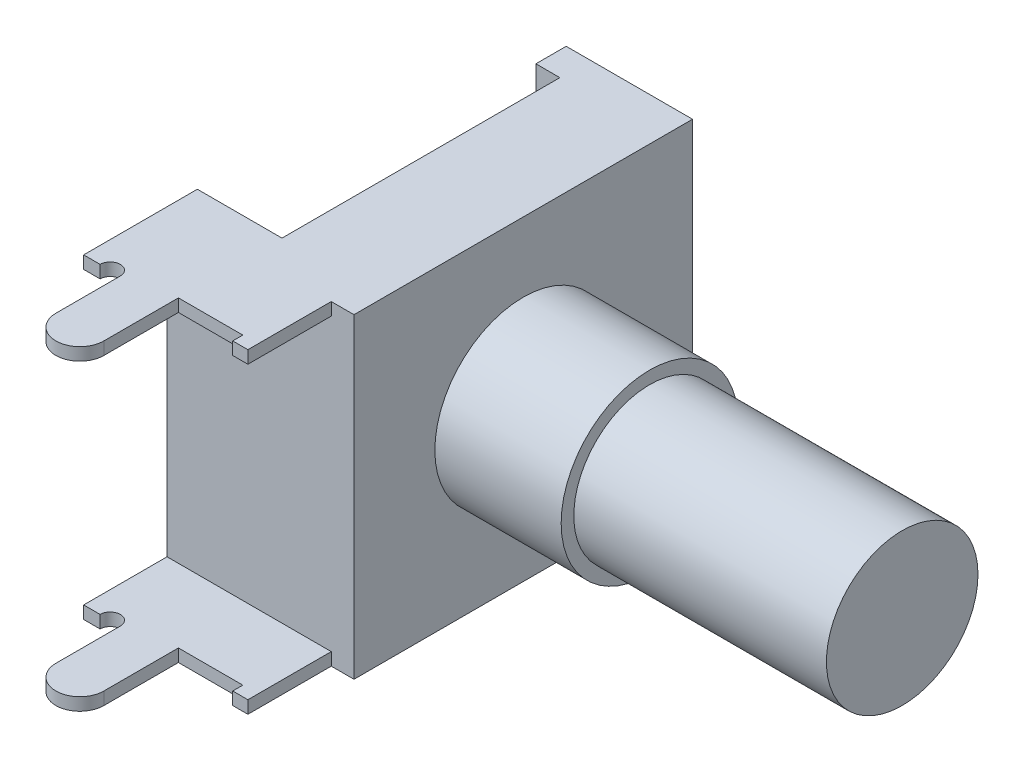
SolidWorks part; units mm, degrees
ref_plane "Front Plane" through (0, 0, 0) normal (0, 0, 1) x (1, 0, 0)
ref_plane "Top Plane" through (0, 0, 0) normal (0, 1, 0) x (1, 0, 0)
ref_plane "Right Plane" through (0, 0, 0) normal (1, 0, 0) x (0, 0, -1)
sketch "Sketch1" plane through (0, 0, 0) normal (0, 1, 0) x (1, 0, 0)
  line L0 (0, 0) -> (0, -60.4668) construction
  line L1 (-2.4, 0) -> (-1.75, 0)
  line L2 (-0.95, 0) -> (-0.95, -2.55)
  line L3 (0.95, -2.55) -> (0.95, 0.4)
  line L4 (-2.4, 0) -> (-2.4, 4.5)
  line L5 (0.95, 0.4) -> (3.5, 0.4)
  line L6 (3.5, 0.4) -> (3.5, 0)
  line L7 (3.5, 0) -> (4.1, 0)
  line L8 (4.1, 0) -> (4.1, 3.3)
  line L9 (0, 10) -> (12.4588, 10) construction
  line L10 (4.1, 3.3) -> (5, 3.3)
  line L11 (5, 3.3) -> (5, 16.7)
  line L12 (5, 16.7) -> (0, 16.7)
  line L13 (0, 16.7) -> (0, 15.5)
  line L14 (0, 15.5) -> (0.95, 15.5)
  line L15 (0.95, 15.5) -> (0.95, 4.5)
  line L16 (0.95, 4.5) -> (-2.4, 4.5)
  arc A0 (-0.95, -2.55) -> (0.95, -2.55) centre (0, -2.55) ccw
  arc A1 (-1.75, 0) -> (-0.95, 0) centre (-1.35, 0) cw
  point P1 (0, -3.5)
  dimension "D5" = 0.4
  dimension "D1" = 13.4
  dimension "D2" = 1.9
  dimension "D3" = 2.4
  dimension "D4" = 4.1
  dimension "D6" = 0.4
  dimension "D7" = 0.6
  dimension "D8" = 10
  dimension "D9" = 5
  dimension "D10" = 3.5
  dimension "D11" = 11
extrude "Boss-Extrude1" add sketch "Sketch1" along normal mid plane 12.5
sketch "Sketch2" plane through (4.1, 0, 0) normal (1, 0, 0) x (0, 0, -1)
  line L0 (3.3, 6.25) -> (3.3, -6.25) construction
  line L1 (3.3, 5.75) -> (-7.0938, 5.75)
  line L2 (3.3, 5.75) -> (3.3, -5.75)
  line L3 (3.3, -5.75) -> (-7.0938, -5.75)
  line L4 (-7.0938, 5.75) -> (-7.0938, -5.75)
  line L5 (0, 0) -> (-7.0938, 0) construction
  line L6 (0, 6.25) -> (0, -6.25) construction
  line L7 (0, -6.25) -> (3.3, -6.25) construction
  dimension "D1" = 0.5
extrude "Cut-Extrude1" cut sketch "Sketch2" against normal through all
sketch "Sketch3" plane through (5, 0, 0) normal (1, 0, 0) x (0, 0, -1)
  line L0 (16.7, 0) -> (3.3, 0) construction
  line L1 (16.7, 6.25) -> (16.7, -6.25) construction
  line L2 (3.3, 6.25) -> (3.3, -6.25) construction
  line L3 (10, 6.25) -> (10, -6.25) construction
  line L4 (3.3, 6.25) -> (16.7, 6.25) construction
  line L5 (3.3, -6.25) -> (16.7, -6.25) construction
  circle A0 centre (10, 0) radius 3.5
  circle A1 centre (10, 0) radius 3
  dimension "D1" = 7
  dimension "D2" = 6
extrude "Boss-Extrude2" add sketch "Sketch3" along normal blind 5 contours A0
extrude "Boss-Extrude3" add sketch "Sketch3<3>" along normal offset from surface (15 mm away) 20 contours A1 up to face at (0, 0, -16.1)
sketch "Sketch3<3>" plane through (5, 0, 0) normal (1, 0, 0) x (0, 0, -1) same geometry as "Sketch3"
